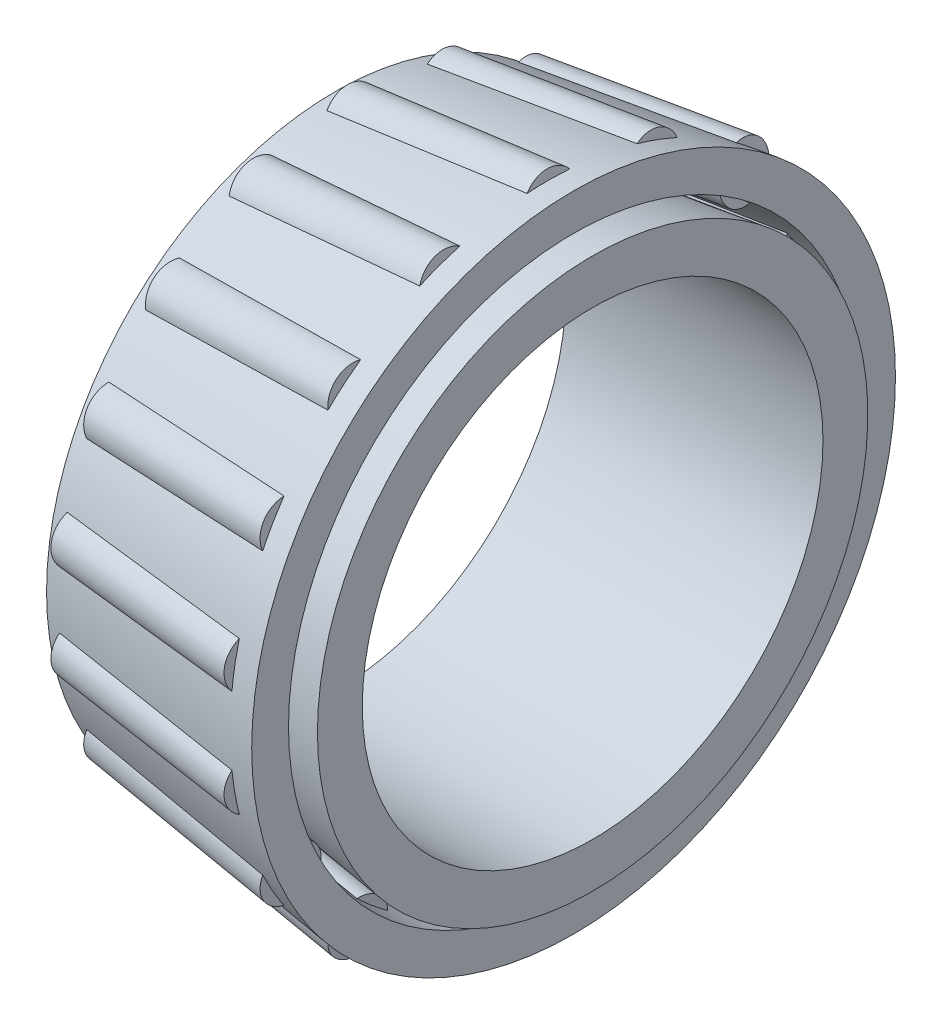
SolidWorks part; units mm, degrees
ref_plane "Front Plane" through (0, 0, 0) normal (0, 0, 1) x (1, 0, 0)
ref_plane "Top Plane" through (0, 0, 0) normal (0, 1, 0) x (1, 0, 0)
ref_plane "Right Plane" through (0, 0, 0) normal (1, 0, 0) x (0, 0, -1)
sketch "Sketch2" plane through (0, 0, 0) normal (0, 0, 1) x (1, 0, 0)
  line L0 (0, 0) -> (0, 14.2875) construction
  line L1 (-7.385, 14.2875) -> (8.5661, 14.2875)
  line L2 (-7.385, 14.2875) -> (-7.385, 14.9733)
  line L3 (-7.385, 14.9733) -> (8.5661, 17.0688)
  line L4 (8.5661, 17.0688) -> (8.5661, 14.2875)
  line L5 (-7.385, 15.7418) -> (7.3851, 17.6822)
  line L6 (7.3851, 17.6822) -> (7.3851, 19.9644)
  line L7 (-7.385, 15.7418) -> (-7.385, 17.9197)
  line L8 (-7.385, 17.9197) -> (7.3851, 19.9644)
  line L9 (-7.385, 16.8308) -> (7.3851, 18.8233) construction
  line L10 (-6.4141, 16.9618) -> (-6.6816, 18.9443)
  line L11 (-6.6816, 18.9443) -> (5.7041, 20.6152)
  line L12 (5.7041, 20.6152) -> (5.9715, 18.6326)
  line L13 (-6.4367, 17.1292) -> (5.9715, 18.8031)
  line L14 (-6.6426, 18.655) -> (5.7431, 20.3259)
  line L16 (-7.385, 0) -> (8.5661, 0) construction
  dimension "D1" = 14.2875
  dimension "D2" = 15.9512
  dimension "D3" = 7.385
  dimension "D4" = 0
  dimension "D5" = 17.0688
  dimension "D6" = 14.9733
  dimension "D7" = 0.762
  dimension "D8" = 17.9197
  dimension "D9" = 19.9644
  dimension "D10" = 14.7701
  dimension "D11" = 0
revolve "Revolve1" add sketch "Sketch2" angle 360 about L16 region at (2.1974, 15.2598, 0) region at (0.2313, 17.5053, 0) region at (-0.2585, 18.4343, 0)
revolve "Cut-Revolve2" cut sketch "Sketch2<8>" angle 360 about L9 region at (-0.4832, 19.1806, 0) region at (-0.2585, 18.4343, 0)
sketch "Sketch2<8>" plane through (0, 0, 0) normal (0, 0, 1) x (1, 0, 0) same geometry as "Sketch2"
pattern_circular "CirPattern1" count 18 over 360 about axis through (-7.385, 0, 0) along (-1, 0, 0) of "Cut-Revolve2"
revolve "Revolve4" add sketch "Sketch2<13>" angle 360 about L9 region at (-0.4832, 19.1806, 0) region at (-0.2585, 18.4343, 0)
sketch "Sketch2<13>" plane through (0, 0, 0) normal (0, 0, 1) x (1, 0, 0) same geometry as "Sketch2"
pattern_circular "CirPattern6" count 18 over 360 about axis through (-7.385, 0, 0) along (-1, 0, 0) of "Revolve4"
